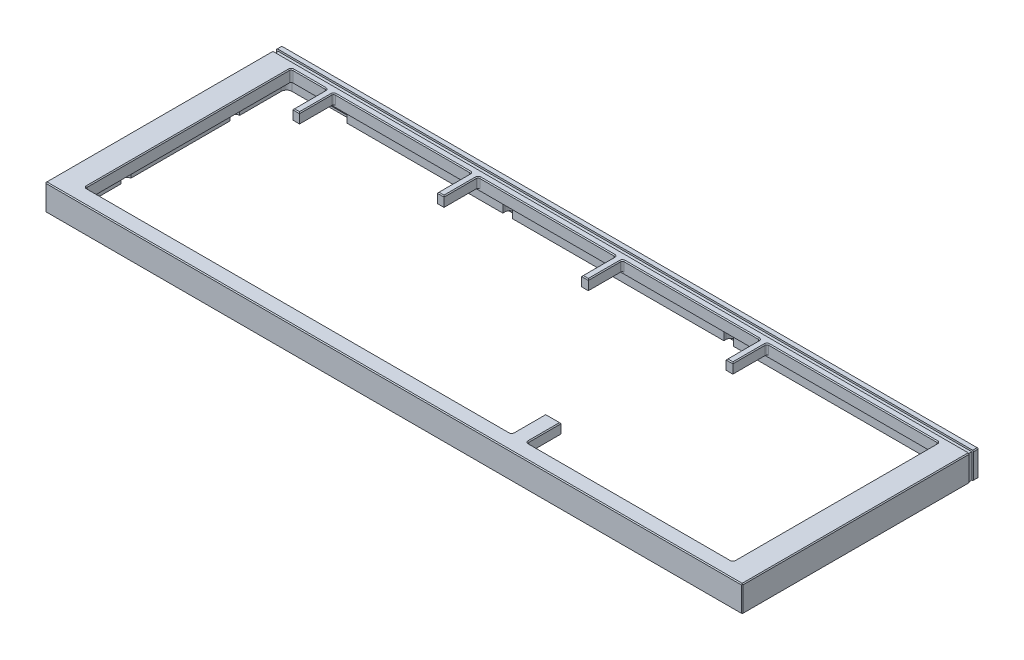
SolidWorks part; units mm, degrees
material "6061-T6 (SS)"
ref_plane "Front Plane" through (0, 0, 0) normal (0, 0, 1) x (1, 0, 0)
ref_plane "Top Plane" through (0, 0, 0) normal (0, 1, 0) x (1, 0, 0)
ref_plane "Right Plane" through (0, 0, 0) normal (1, 0, 0) x (0, 0, -1)
sketch "Sketch1" plane through (0, 0, 0) normal (0, 1, 0) x (1, 0, 0)
  line L1 (0, 0) -> (390.74, 0)
  line L2 (0, 0) -> (0, 132.7)
  line L3 (0, 132.7) -> (390.74, 132.7)
  line L4 (390.74, 0) -> (390.74, 132.7)
  line L5 (13.92, 124) -> (376.82, 124)
  line L6 (13.92, 124) -> (13.92, 8.7)
  line L7 (13.92, 8.7) -> (376.82, 8.7)
  line L8 (376.82, 124) -> (376.82, 8.7)
  point P9 (195.37, 124)
  point P10 (195.37, 132.7)
  point P11 (13.92, 66.35)
  point P12 (0, 66.35)
  dimension "D1" = 362.9
  dimension "D2" = 115.3
  dimension "D3" = 8.7
  dimension "D4" = 13.92
extrude "Main Body" add sketch "Sketch1" along normal blind 14.8
sketch "Sketch2" plane through (0, 0, 0) normal (0, -1, 0) x (1, 0, 0)
  line L0 (390.74, -132.7) -> (0, -132.7) construction
  line L1 (388.74, -130.7) -> (2, -130.7)
  line L2 (388.74, -130.7) -> (388.74, -2)
  line L3 (388.74, -2) -> (2, -2)
  line L4 (2, -130.7) -> (2, -2)
  line L5 (390.74, 0) -> (390.74, -132.7) construction
  point P4 (195.37, -130.7)
  point P7 (195.37, -132.7)
  point P8 (388.74, -66.35)
  point P11 (390.74, -66.35)
  dimension "D1" = 2
  dimension "D2" = 2
extrude "Alignment Guide" cut sketch "Sketch2" against normal blind 2 contours L2 L1 L4 L3
sketch "Sketch3" plane through (0, 14.8, 0) normal (0, 1, 0) x (1, 0, 0)
  line L0 (13.92, 8.7) -> (376.82, 8.7) construction
  line L1 (252.82, 27.8) -> (261.52, 27.8)
  line L2 (252.82, 27.8) -> (252.82, 8.7)
  line L3 (252.82, 8.7) -> (261.52, 8.7)
  line L4 (261.52, 27.8) -> (261.52, 8.7)
  line L5 (376.82, 8.7) -> (376.82, 124) construction
  line L6 (376.82, 124) -> (13.92, 124) construction
  line L7 (33.92, 124) -> (37.72, 124)
  line L8 (33.92, 124) -> (33.92, 104.9)
  line L9 (33.92, 104.9) -> (37.72, 104.9)
  line L10 (37.72, 124) -> (37.72, 104.9)
  line L11 (13.92, 124) -> (13.92, 8.7) construction
  line L12 (114.92, 124) -> (118.72, 124)
  line L13 (114.92, 124) -> (114.92, 104.9)
  line L14 (114.92, 104.9) -> (118.72, 104.9)
  line L15 (118.72, 124) -> (118.72, 104.9)
  line L16 (195.82, 124) -> (199.62, 124)
  line L17 (195.82, 124) -> (195.82, 104.9)
  line L18 (195.82, 104.9) -> (199.62, 104.9)
  line L19 (199.62, 124) -> (199.62, 104.9)
  line L20 (276.82, 124) -> (280.62, 124)
  line L21 (276.82, 124) -> (276.82, 104.9)
  line L22 (276.82, 104.9) -> (280.62, 104.9)
  line L23 (280.62, 124) -> (280.62, 104.9)
  point P8 (257.17, 8.7)
  dimension "D1" = 115.3
  dimension "D2" = 124
  dimension "D3" = 19.1
  dimension "D4" = 3.8
  dimension "D5" = 19.1
  dimension "D6" = 77.2
  dimension "D7" = 77.1
  dimension "D8" = 77.2
  dimension "D9" = 20
extrude "Blockers" add sketch "Sketch3" against normal blind 5.5
fillet "Fillet5" radius 1 14 edges at (280.62, 12.05, -124) (276.82, 12.05, -124) (195.82, 12.05, -124) (199.62, 12.05, -124) (118.72, 12.05, -124) (114.92, 12.05, -124) (33.92, 12.05, -124) (37.72, 12.05, -124) (13.92, 8.4, -124) (13.92, 8.4, -8.7) (252.82, 12.05, -8.7) (261.52, 12.05, -8.7) (376.82, 8.4, -8.7) (376.82, 8.4, -124)
sketch "Sketch4" plane through (0, 2, 0) normal (0, -1, 0) x (1, 0, 0)
  line L0 (0, 0) -> (390.74, 0) construction
  line L1 (381.27, -125.9) -> (9.47, -125.9)
  line L2 (381.27, -125.9) -> (381.27, -6.8)
  line L3 (381.27, -6.8) -> (9.47, -6.8)
  line L4 (9.47, -125.9) -> (9.47, -6.8)
  line L5 (390.74, 0) -> (390.74, -132.7) construction
  point P4 (195.37, -6.8)
  point P7 (195.37, 0)
  point P8 (381.27, -66.35)
  point P11 (390.74, -66.35)
  dimension "D1" = 119.1
  dimension "D2" = 371.8
extrude "PCB Cutout" cut sketch "Sketch4" against normal offset from surface (6.3 mm away) 6.5 up to face at (195.37, 14.8, -66.35)
fillet "Fillet4" radius 3 8 edges at (9.47, 5.15, -6.8) (9.47, 5.15, -125.9) (381.27, 5.15, -125.9) (381.27, 5.15, -6.8) (2, 1, -130.7) (2, 1, -2) (388.74, 1, -2) (388.74, 1, -130.7)
sketch "Sketch6" plane through (0, 2, 0) normal (0, -1, 0) x (1, 0, 0)
  line L0 (381.27, -9.8) -> (381.27, -122.9) construction
  line L1 (254.59, -127.1) -> (260.09, -127.1)
  line L2 (254.59, -127.1) -> (254.59, -125.9)
  line L3 (254.59, -125.9) -> (260.09, -125.9)
  line L4 (260.09, -127.1) -> (260.09, -125.9)
  line L5 (12.47, -125.9) -> (378.27, -125.9) construction
  line L11 (378.27, -6.8) -> (12.47, -6.8) construction
  line L16 (260.09, -6.8) -> (254.59, -6.8)
  line L17 (260.09, -6.8) -> (260.09, -4.8)
  line L18 (260.09, -4.8) -> (254.59, -4.8)
  line L19 (254.59, -6.8) -> (254.59, -4.8)
  line L21 (0, 0) -> (390.74, 0) construction
  line L24 (390.74, -66.35) -> (195.37, -66.35) construction
  line L25 (390.74, 0) -> (390.74, -132.7) construction
  line L26 (328.6755, -66.35) -> (328.6755, -130.7) construction
  line L27 (385.74, -130.7) -> (5, -130.7) construction
  line L28 (328.6755, -66.35) -> (328.6755, -8.7) construction
  line L29 (375.82, -8.7) -> (14.92, -8.7) construction
  line L55 (390.74, -132.7) -> (0, -132.7) construction
  line L56 (195.37, -132.7) -> (195.37, 0) construction
  line L57 (136.15, -6.8) -> (136.15, -4.8)
  line L58 (130.65, -4.8) -> (136.15, -4.8)
  line L59 (130.65, -6.8) -> (130.65, -4.8)
  line L60 (130.65, -6.8) -> (136.15, -6.8)
  line L61 (130.65, -127.1) -> (130.65, -125.9)
  line L62 (136.15, -125.9) -> (130.65, -125.9)
  line L63 (136.15, -127.1) -> (136.15, -125.9)
  line L64 (136.15, -127.1) -> (130.65, -127.1)
  circle A0 centre (381.07, -96.85) radius 2.75
  circle A1 centre (381.07, -35.85) radius 2.75
  circle A2 centre (257.34, -4.8) radius 2.75
  circle A3 centre (257.34, -127.1) radius 2.75
  circle A8 centre (133.4, -4.8) radius 2.75
  circle A9 centre (9.67, -35.85) radius 2.75
  circle A10 centre (9.67, -96.85) radius 2.75
  circle A11 centre (133.4, -127.1) radius 2.75
  point P25 (195.37, -66.35)
  point P32 (257.34, -125.9)
  point P33 (257.34, -6.8)
  line M17 (12.47, -6.8) -> (378.27, -6.8)
  line M18 (381.27, -9.8) -> (381.27, -122.9)
  line M19 (378.27, -125.9) -> (12.47, -125.9)
  line M20 (9.47, -122.9) -> (9.47, -9.8)
  dimension "D4" = 5.5
  dimension "D5" = 133.4
  dimension "D1" = 30.5
  dimension "D2" = 4.8
  dimension "D3" = 30.5
  dimension "D6" = 0.2
  dimension "D7" = 5.6
extrude "PlateTabs" cut sketch "Sketch6" against normal up to surface (6.3 mm away) contours A0 M18 | A1 M18 | A2 L19 M17 | L16 A2 L18 | A2 L17 M17 | L18 A2 | L1 A3 | L1 A3 L3 | A3 L2 M19 | A11 L64 | A11 L64 L62 | A10 M20 | A9 M20 | A8 L58 | A8 L60 L58 | A3 L4 M19 | A8 L59 M17 | L57 A8 M17 | A11 L63 M19 | L61 A11 M19 | A11 | L59 L58 L57 L60 | A3 region at (257.34, 2, -126.5102) region at (136.0681, 2, -126.1969) region at (257.34, 2, -128.2671) region at (254.6719, 2, -126.1969) region at (260.0081, 2, -126.1969) region at (133.4, 2, -126.5102) region at (133.4, 2, -128.2671) region at (130.7319, 2, -126.1969) region at (135.9001, 2, -6.317) region at (259.8401, 2, -6.317) region at (257.34, 2, -5.7445) region at (257.34, 2, -3.6329) region at (254.8399, 2, -6.317) region at (133.4, 2, -5.7445) region at (133.4, 2, -3.6329) region at (130.8999, 2, -6.317) region at (382.3459, 2, -96.85) region at (382.3459, 2, -35.85) region at (8.3941, 2, -96.85) region at (8.3941, 2, -35.85) up to face at (195.37, 8.3, -66.35)
sketch "Sketch9" plane through (0, 0, -132.7) normal (0, 0, -1) x (-1, 0, 0)
  line L1 (-40.9, 2.4) -> (-30.9, 2.4)
  line L2 (-40.9, 2.4) -> (-40.9, 7.4)
  line L3 (-40.9, 7.4) -> (-30.9, 7.4)
  line L4 (-30.9, 2.4) -> (-30.9, 7.4)
  line L7 (0, 14.8) -> (0, 0) construction
  line L8 (-390.74, 0) -> (0, 0) construction
  point P4 (-30.9, 4.9)
  point P6 (-35.9, 7.4)
  dimension "D1" = 4.9
  dimension "D2" = 5
  dimension "D3" = 10
  dimension "D4" = 35.9
extrude "USB Cutout" cut sketch "Sketch9" against normal up to surface (8.7 mm away) up to face at (164.89, 11.95, -124)
sketch "Sketch10" plane through (0, 0, -132.7) normal (0, 0, -1) x (-1, 0, 0)
  line L0 (-30.9, 7.4) -> (-40.9, 7.4) construction
  line L1 (-42.4, 8.9) -> (-29.4, 8.9)
  line L2 (-42.4, 8.9) -> (-42.4, 0.9)
  line L3 (-42.4, 0.9) -> (-29.4, 0.9)
  line L4 (-29.4, 8.9) -> (-29.4, 0.9)
  line L5 (-40.9, 7.4) -> (-40.9, 2.4) construction
  point P4 (-35.9, 8.9)
  point P7 (-35.9, 7.4)
  point P10 (-40.9, 4.9)
  point P11 (-42.4, 4.9)
  dimension "D1" = 1.5
  dimension "D2" = 1.5
extrude "USB Outline" cut sketch "Sketch10" against normal blind 1
sketch "Sketch11" plane through (0, 0, -125.9) normal (0, 0, 1) x (1, 0, 0)
  line L1 (43.4, 2) -> (28.4, 2)
  line L2 (43.4, 2) -> (43.4, 7.4)
  line L3 (43.4, 7.4) -> (28.4, 7.4)
  line L4 (28.4, 2) -> (28.4, 7.4)
  line L5 (30.9, 7.4) -> (40.9, 7.4) construction
  line L6 (40.9, 2.4) -> (30.9, 2.4) construction
  line L7 (12.47, 2) -> (130.65, 2) construction
  point P8 (35.9, 2)
  point P11 (35.9, 2.4)
  dimension "D1" = 15
extrude "PCB Clearance" cut sketch "Sketch11" against normal blind 3.9
fillet "Fillet6" radius 1.5 8 edges at (40.9, 7.4, -130.75) (30.9, 7.4, -130.75) (40.9, 2.4, -130.75) (42.4, 0.9, -132.2) (42.4, 8.9, -132.2) (29.4, 8.9, -132.2) (30.9, 2.4, -130.75) (29.4, 0.9, -132.2)
fillet "Fillet7" radius 2.5 2 edges at (28.4, 4.7, -129.8) (43.4, 4.7, -129.8)
sketch "Sketch12" plane through (0, 8.3, 0) normal (0, -1, 0) x (1, 0, 0)
  line L0 (195.37, -132.7) -> (195.37, 0) construction
  line L1 (390.74, -132.7) -> (0, -132.7) construction
  line L2 (14.92, -124) -> (375.82, -124) construction
  line L3 (0, 0) -> (390.74, 0) construction
  line L4 (390.74, 0) -> (390.74, -132.7) construction
  line L8 (376.82, -123) -> (376.82, -9.7) construction
  line L9 (375.82, -8.7) -> (14.92, -8.7) construction
  arc A0 (381.27, -38.5927) -> (381.27, -33.1073) centre (381.07, -35.85) ccw construction
  arc A1 (381.27, -99.5927) -> (381.27, -94.1073) centre (381.07, -96.85) ccw construction
  point P0 (257.34, -127.1)
  point P1 (381.42, -96.85)
  point P2 (381.42, -35.85)
  point P3 (257.34, -4.8)
  point P8 (133.4, -4.8)
  point P10 (9.32, -35.85)
  point P14 (9.32, -96.85)
  point P16 (133.4, -127.1)
  point P34 (383.82, -35.85)
  point P39 (383.82, -96.85)
  dimension "D1" = 3.1
  dimension "D2" = 3.9
  dimension "D3" = 4.6
  dimension "D4" = 133.4
sketch "Sketch14" plane through (0, 2, 0) normal (0, -1, 0) x (1, 0, 0)
  line L0 (195.37, -132.7) -> (195.37, 0) construction
  line L1 (390.74, -132.7) -> (0, -132.7) construction
  line L2 (0, 0) -> (390.74, 0) construction
  line L5 (195.37, -66.35) -> (390.74, -66.35) construction
  line L6 (390.74, 0) -> (390.74, -132.7) construction
  line L7 (388.74, -127.7) -> (388.74, -5) construction
  line L8 (385.74, -130.7) -> (5, -130.7) construction
  line L9 (385.74, -2) -> (5, -2) construction
  point P8 (385.04, -111.35)
  point P9 (385.04, -66.35)
  point P10 (385.04, -21.35)
  point P11 (280.74, -4.4)
  point P20 (280.74, -128.3)
  point P22 (110, -4.4)
  point P28 (110, -128.3)
  point P29 (5.7, -21.35)
  point P30 (5.7, -66.35)
  point P31 (5.7, -111.35)
  dimension "D1" = 2.4
  dimension "D2" = 2.4
  dimension "D3" = 110
  dimension "D4" = 45
  dimension "D5" = 45
  dimension "D6" = 3.7
chamfer "Chamfer1" distance 0.5 42 edges at (14.2129, 14.8, -8.9929) (133.37, 14.8, -8.7) (252.5271, 14.8, -8.9929) (252.82, 14.8, -18.75) (257.17, 14.8, -27.8) (261.52, 14.8, -18.75) (261.8129, 14.8, -8.9929) (319.17, 14.8, -8.7) (376.5271, 14.8, -8.9929) (376.82, 14.8, -66.35) (376.5271, 14.8, -123.7071) (328.72, 14.8, -124) (280.9129, 14.8, -123.7071) (280.62, 14.8, -113.95) (278.72, 14.8, -104.9) (276.82, 14.8, -113.95) (276.5271, 14.8, -123.7071) (238.22, 14.8, -124) (199.9129, 14.8, -123.7071) (199.62, 14.8, -113.95) (197.72, 14.8, -104.9) (195.82, 14.8, -113.95) (195.5271, 14.8, -123.7071) (157.27, 14.8, -124) (119.0129, 14.8, -123.7071) (118.72, 14.8, -113.95) (116.82, 14.8, -104.9) (114.92, 14.8, -113.95) (114.6271, 14.8, -123.7071) (76.32, 14.8, -124) (38.0129, 14.8, -123.7071) (37.72, 14.8, -113.95) (35.82, 14.8, -104.9) (33.92, 14.8, -113.95) (33.6271, 14.8, -123.7071) (23.92, 14.8, -124) (14.2129, 14.8, -123.7071) (13.92, 14.8, -66.35) (195.37, 14.8, -132.7) (390.74, 14.8, -66.35) (195.37, 14.8, 0) (0, 14.8, -66.35)
chamfer "Chamfer2" distance 0.5 8 edges at (0, 7.15, -132.7) (195.37, 0, -132.7) (390.74, 7.15, -132.7) (390.74, 0, -66.35) (390.74, 7.15, 0) (0, 7.15, 0) (195.37, 0, 0) (0, 0, -66.35)
sketch "Sketch27" plane through (0, 14.8, 0) normal (0, 1, 0) x (1, 0, 0)
  line L0 (0, 0.5) -> (0, 132.2) construction
  line L1 (0, 129.7) -> (390.74, 129.7)
  line L2 (0, 129.7) -> (0, 127.2)
  line L3 (0, 127.2) -> (390.74, 127.2)
  line L4 (390.74, 129.7) -> (390.74, 127.2)
  line L5 (390.74, 132.2) -> (390.74, 0.5) construction
  line L8 (0.5, 132.7) -> (390.24, 132.7) construction
  dimension "D1" = 2.5
  dimension "D2" = 3
extrude "Cut-Extrude11" cut sketch "Sketch27" against normal blind 1
sketch "Sketch28" plane through (0, 13.8, 0) normal (0, 1, 0) x (1, 0, 0)
  line L1 (0, 129.7) -> (1, 129.7)
  line L2 (0, 129.7) -> (0, 127.2)
  line L3 (0, 127.2) -> (1, 127.2)
  line L4 (1, 129.7) -> (1, 127.2)
  line L5 (389.74, 129.7) -> (390.74, 129.7)
  line L6 (389.74, 129.7) -> (389.74, 127.2)
  line L7 (389.74, 127.2) -> (390.74, 127.2)
  line L8 (390.74, 129.7) -> (390.74, 127.2)
  line L9 (390.74, 129.7) -> (0, 129.7) construction
  line L10 (0, 127.2) -> (390.74, 127.2) construction
  dimension "D1" = 1
  dimension "D2" = 1
extrude "Cut-Extrude12" cut sketch "Sketch28" against normal through all
sketch "Sketch21" [suppressed] plane through (0, 14.8, 0) normal (0, 1, 0) x (1, 0, 0)
  line L0 (0.5, 132.7) -> (390.24, 132.7) construction
  line L1 (382.53, 132.7) -> (385.03, 132.7)
  line L2 (382.53, 132.7) -> (382.53, 72.7)
  line L3 (382.53, 72.7) -> (385.03, 72.7)
  line L4 (385.03, 132.7) -> (385.03, 72.7)
  line L5 (390.74, 132.2) -> (390.74, 129.7) construction
  line L6 (390.74, 129.1) -> (294.74, 129.1)
  line L7 (390.74, 129.1) -> (390.74, 127.6)
  line L8 (390.74, 127.6) -> (294.74, 127.6)
  line L9 (294.74, 129.1) -> (294.74, 127.6)
  line L10 (362.9081, 132.2) -> (362.9081, 124.5) construction
  line L11 (390.24, 132.2) -> (0.5, 132.2) construction
  line L12 (281.62, 124.5) -> (375.82, 124.5) construction
  line L13 (365.5702, 129.1) -> (365.5702, 127.6) construction
  line L14 (377.32, 119.5259) -> (390.24, 119.5259) construction
  line L15 (377.32, 123) -> (377.32, 9.7) construction
  line L16 (390.24, 0.5) -> (390.24, 127.2) construction
  line L17 (382.53, 116.0504) -> (385.03, 116.0504) construction
  point P28 (383.78, 116.0504)
  point P29 (383.78, 119.5259)
  point P30 (365.5702, 128.35)
  point P31 (362.9081, 128.35)
  dimension "D1" = 2.5
  dimension "D2" = 1.5
  dimension "D3" = 60
  dimension "D4" = 96
extrude "Cut-Extrude5" [suppressed] cut sketch "Sketch21" against normal blind 1 contours L4 L3 L2 L1 | L8 L9 L6 L7
sketch "Sketch23" [suppressed] plane through (390.74, 0, 0) normal (1, 0, 0) x (0, 0, -1)
  line L0 (129.1, 13.8) -> (129.1, 14.3) construction
  line L1 (127.6, 13.8) -> (129.1, 13.8)
  line L2 (127.6, 13.8) -> (127.6, 0)
  line L3 (127.6, 0) -> (129.1, 0)
  line L4 (129.1, 13.8) -> (129.1, 0)
extrude "Cut-Extrude6" [suppressed] cut sketch "Sketch23" against normal blind 1
sketch "Sketch20" plane through (0, 14.8, 0) normal (0, 1, 0) x (1, 0, 0)
  line L0 (0, 0.5) -> (0, 127.2) construction
  line L1 (0, 129.1) -> (390.74, 129.1)
  line L2 (0, 129.1) -> (0, 127.6)
  line L3 (0, 127.6) -> (390.74, 127.6)
  line L4 (390.74, 129.1) -> (390.74, 127.6)
  line L5 (390.74, 132.2) -> (390.74, 129.7) construction
  line L6 (0.5, 132.7) -> (390.24, 132.7) construction
  line L7 (381.7523, 132.7) -> (384.2523, 132.7)
  line L8 (381.7523, 132.7) -> (381.7523, 0)
  line L9 (381.7523, 0) -> (384.2523, 0)
  line L10 (384.2523, 132.7) -> (384.2523, 0)
  line L11 (390.24, 0) -> (0.5, 0) construction
  line L12 (376.82, 111.1489) -> (390.74, 111.1489) construction
  line L13 (376.82, 9.7) -> (376.82, 123) construction
  line L14 (381.7523, 114.604) -> (384.2523, 114.604) construction
  line L15 (369.2566, 124.5) -> (369.2566, 132.2) construction
  line L16 (281.62, 124.5) -> (375.82, 124.5) construction
  line L17 (390.24, 132.2) -> (0.5, 132.2) construction
  line L18 (371.0168, 127.6) -> (371.0168, 129.1) construction
  point P30 (371.0168, 128.35)
  point P31 (369.2566, 128.35)
  dimension "D1" = 2.5
  dimension "D2" = 1.5
extrude "Cut-Extrude4" [suppressed] cut sketch "Sketch20" against normal blind 1
sketch "Sketch19" plane through (0, 14.8, 0) normal (0, 1, 0) x (1, 0, 0)
  line L0 (0.5, 132.7) -> (390.24, 132.7) construction
  line L1 (5.46, 132.7) -> (8.46, 132.7)
  line L2 (5.46, 132.7) -> (5.46, 0)
  line L3 (5.46, 0) -> (8.46, 0)
  line L4 (8.46, 132.7) -> (8.46, 0)
  line L7 (382.28, 132.7) -> (385.28, 132.7)
  line L8 (382.28, 132.7) -> (382.28, 0)
  line L9 (382.28, 0) -> (385.28, 0)
  line L10 (385.28, 132.7) -> (385.28, 0)
  line L11 (390.24, 0) -> (0.5, 0) construction
  line L12 (377.32, 110.209) -> (390.24, 110.209) construction
  line L13 (377.32, 123) -> (377.32, 9.7) construction
  line L14 (390.24, 0.5) -> (390.24, 127.2) construction
  line L15 (382.28, 106.8719) -> (385.28, 106.8719) construction
  line L16 (0.5, 106.8719) -> (13.42, 106.8719) construction
  line L17 (0.5, 132.2) -> (0.5, 129.7) construction
  line L18 (13.42, 9.7) -> (13.42, 123) construction
  line L19 (5.46, 102.7297) -> (8.46, 102.7297) construction
  point P12 (383.78, 106.8719)
  point P14 (383.78, 110.209)
  point P30 (6.96, 102.7297)
  point P31 (6.96, 106.8719)
  dimension "D1" = 3
  dimension "D2" = 3
extrude "Cut-Extrude3" [suppressed] cut sketch "Sketch19" against normal blind 1
sketch "Sketch17" plane through (0, 14.8, 0) normal (0, 1, 0) x (1, 0, 0)
  line L0 (390.24, 0.5) -> (390.24, 127.2) construction
  line L1 (5.71, 129.6) -> (385.03, 129.6)
  line L2 (5.71, 129.6) -> (5.71, -1.9)
  line L3 (5.71, -1.9) -> (385.03, -1.9)
  line L4 (385.03, 129.6) -> (385.03, -1.9)
  line L5 (8.21, 127.1) -> (382.53, 127.1)
  line L6 (8.21, 127.1) -> (8.21, 0.6)
  line L7 (8.21, 0.6) -> (382.53, 0.6)
  line L8 (382.53, 127.1) -> (382.53, 0.6)
  line L9 (390.24, 132.2) -> (0.5, 132.2) construction
  line L10 (21.2533, 132.2) -> (21.2533, 124.5) construction
  line L11 (14.92, 124.5) -> (32.92, 124.5) construction
  line L12 (25.2757, 129.6) -> (25.2757, 127.1) construction
  line L13 (0.5, 116.1326) -> (13.42, 116.1326) construction
  line L14 (0.5, 132.2) -> (0.5, 129.7) construction
  line L15 (13.42, 9.7) -> (13.42, 123) construction
  line L16 (5.71, 120.1548) -> (8.21, 120.1548) construction
  point P8 (382.53, 63.85)
  point P9 (385.03, 63.85)
  point P12 (390.24, 63.85)
  point P13 (195.37, 129.6)
  point P14 (195.37, 127.1)
  point P17 (195.37, 132.2)
  point P24 (25.2757, 128.35)
  point P25 (21.2533, 128.35)
  point P34 (6.96, 116.1326)
  point P35 (6.96, 120.1548)
  dimension "D1" = 2.5
  dimension "D2" = 2.5
extrude "Cut-Extrude1" [suppressed] cut sketch "Sketch17" against normal blind 1
hole_wizard "M3x0.5 Tapped Hole1" positions "3DSketch1" profile "Sketch29" tap size "M3x0.5" standard "ANSI Metric"
sketch3d "3DSketch1"
  point P0 (385.04, 2, -111.35)
  point P3 (385.04, 2, -21.35)
  point P6 (280.74, 2, -4.4)
  point P9 (110, 2, -4.4)
  point P12 (5.7, 2, -21.35)
  point P15 (5.7, 2, -66.35)
  point P18 (5.7, 2, -111.35)
  point P21 (110, 2, -128.3)
  point P24 (280.74, 2, -128.3)
  point P28 (385.04, 2, -66.35)
sketch "Sketch29" plane through (385.04, 2, -111.35) normal (1, 0, 0) x (0, 0, -1)
  line L0 (0, 0) -> (0, 4.7511)
  line L1 (0, 4.7511) -> (1.25, 4)
  line L2 (1.25, 4) -> (1.25, 0)
  line L5 (1.25, 0) -> (0, 0)
  line L10 (0, 4.7511) -> (-1.25, 4) construction
  line L11 (0, -6.35) -> (0, 107.95) construction
  dimension "Tap Drill Dia." = 2.5
  dimension "Tap Drill Depth" = 4
  dimension "Drill Angle" = 118
cosmetic thread "Hole Thread1" parameters "D1"=4, "D2"=3
cosmetic thread "Hole Thread2" parameters "D1"=4, "D2"=3
cosmetic thread "Hole Thread3" parameters "D1"=4, "D2"=3
cosmetic thread "Hole Thread4" parameters "D1"=4, "D2"=3
cosmetic thread "Hole Thread5" parameters "D1"=4, "D2"=3
cosmetic thread "Hole Thread6" parameters "D1"=4, "D2"=3
cosmetic thread "Hole Thread7" parameters "D1"=4, "D2"=3
cosmetic thread "Hole Thread8" parameters "D1"=4, "D2"=3
cosmetic thread "Hole Thread9" parameters "D1"=4, "D2"=3
cosmetic thread "Hole Thread18" parameters "D1"=4, "D2"=3
hole_wizard "M2x0.4 Tapped Hole1" positions "3DSketch3" profile "Sketch31" tap size "M2x0.4" standard "ANSI Metric"
sketch3d "3DSketch3"
  point P0 (381.42, 8.3, -96.85)
  point P3 (381.42, 8.3, -35.85)
  point P7 (257.34, 8.3, -4.8)
  point P10 (133.4, 8.3, -4.8)
  point P13 (9.32, 8.3, -35.85)
  point P16 (9.32, 8.3, -96.85)
  point P19 (133.4, 8.3, -127.1)
  point P22 (257.34, 8.3, -127.1)
sketch "Sketch31" plane through (381.42, 8.3, -96.85) normal (1, 0, 0) x (0, 0, -1)
  line L0 (0, 0) -> (0, 4.4807)
  line L1 (0, 4.4807) -> (0.8, 4)
  line L2 (0.8, 4) -> (0.8, 0)
  line L5 (0.8, 0) -> (0, 0)
  line L10 (0, 4.4807) -> (-0.8, 4) construction
  line L11 (0, -6.35) -> (0, 107.95) construction
  dimension "Tap Drill Dia." = 1.6
  dimension "Tap Drill Depth" = 4
  dimension "Drill Angle" = 118
cosmetic thread "Hole Thread19" parameters "D1"=4, "D2"=2
cosmetic thread "Hole Thread20" parameters "D1"=4, "D2"=2
cosmetic thread "Hole Thread21" parameters "D1"=4, "D2"=2
cosmetic thread "Hole Thread22" parameters "D1"=4, "D2"=2
cosmetic thread "Hole Thread23" parameters "D1"=4, "D2"=2
cosmetic thread "Hole Thread24" parameters "D1"=4, "D2"=2
cosmetic thread "Hole Thread25" parameters "D1"=4, "D2"=2
cosmetic thread "Hole Thread26" parameters "D1"=4, "D2"=2
